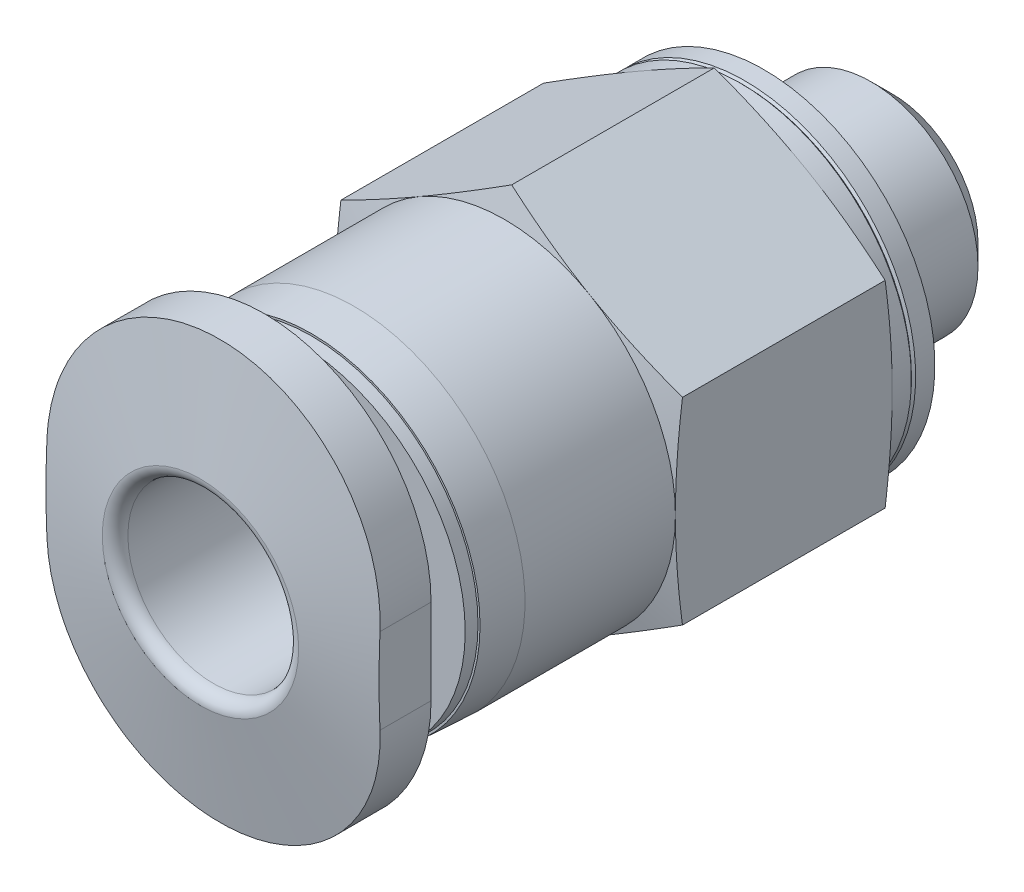
SolidWorks part; units mm, degrees
ref_plane "Front Plane" through (0, 0, 0) normal (0, 0, 1) x (1, 0, 0)
ref_plane "Top Plane" through (0, 0, 0) normal (0, 1, 0) x (1, 0, 0)
ref_plane "Right Plane" through (0, 0, 0) normal (1, 0, 0) x (0, 0, -1)
sketch "Sketch1" plane through (0, 0, 0) normal (1, 0, 0) x (0, 0, -1)
  line L0 (-13.2, 0) -> (-13.2, 2.3)
  line L1 (-13.2, 2.3) -> (-12.7354, 4.9347)
  line L2 (-12.5385, 5.1) -> (-11.7, 5.1)
  line L3 (-11.7, 5.1) -> (-11.7, 3.075)
  line L4 (-11.325, 2.7) -> (-10.9, 2.7)
  line L5 (-10.9, 2.7) -> (-10.9, 3.9)
  line L6 (-10.9, 3.9) -> (-10.6, 3.9)
  line L7 (-10.6, 3.9) -> (-10.6, 3.9476)
  line L8 (-10.6, 3.9476) -> (-9.6, 4)
  line L9 (-9.6, 4) -> (-6.0769, 4)
  line L10 (-6.0769, 4) -> (-5.9054, 4.64)
  line L11 (-5.9054, 4.64) -> (-1.1715, 4.64)
  line L12 (-1.1715, 4.64) -> (-1, 4)
  line L13 (-1, 4) -> (-0.55, 4)
  line L14 (-0.55, 4) -> (-0.5, 3.95)
  line L15 (-0.5, 3.95) -> (-0.45, 4)
  line L16 (-0.45, 4) -> (0, 4)
  line L17 (0, 4) -> (0, 0)
  line L18 (0, 0) -> (-13.2, 0)
  line L19 (0, 0) -> (-13.2, 0) construction
  arc A0 (-12.7354, 4.9347) -> (-12.5385, 5.1) centre (-12.5385, 4.9) cw
  arc A1 (-11.7, 3.075) -> (-11.325, 2.7) centre (-11.325, 3.075) ccw
revolve "Revolve1" add sketch "Sketch1" angle 360 about L19
ref_plane "Plane1" through (-13.2, 0, 0) normal (1, 0, 0) x (0, 0, -1)
ref_plane "Plane2" through (0, 0, 13.2) normal (0, 0, 1) x (1, 0, 0)
ref_plane "Plane3" through (0, 0, 9.7) normal (0, 0, 1) x (1, 0, 0)
sketch "Sketch2" plane through (0, 0, 13.2) normal (0, 0, 1) x (1, 0, 0)
  line L0 (-5.88, -3.3948) -> (0, -6.7896)
  line L1 (0, -6.7896) -> (5.88, -3.3948)
  line L2 (5.88, -3.3948) -> (5.88, 3.3948)
  line L3 (5.88, 3.3948) -> (0, 6.7896)
  line L4 (0, 6.7896) -> (-5.88, 3.3948)
  line L5 (-5.88, 3.3948) -> (-5.88, -3.3948)
  line L6 (-3.9, 1) -> (-3.9, -1)
  line L7 (3.9, -1) -> (3.9, 1)
  arc A0 (-3.9, -1) -> (0, -4.9) centre (0, -1) ccw
  arc A1 (0, -4.9) -> (3.9, -1) centre (0, -1) ccw
  arc A2 (3.9, 1) -> (0, 4.9) centre (0, 1) ccw
  arc A3 (0, 4.9) -> (-3.9, 1) centre (0, 1) ccw
extrude "Cut-Extrude1" cut sketch "Sketch2" against normal blind 1.5
sketch "Sketch3" plane through (0, 0, 0) normal (0, 0, 1) x (1, 0, 0)
  line L0 (-8, -8) -> (8, -8)
  line L1 (8, -8) -> (8, 8)
  line L2 (8, 8) -> (-8, 8)
  line L3 (-8, 8) -> (-8, -8)
  line L4 (-4, -2.3094) -> (0, -4.6188)
  line L5 (0, -4.6188) -> (4, -2.3094)
  line L6 (4, -2.3094) -> (4, 2.3094)
  line L7 (4, 2.3094) -> (0, 4.6188)
  line L8 (0, 4.6188) -> (-4, 2.3094)
  line L9 (-4, 2.3094) -> (-4, -2.3094)
extrude "Cut-Extrude2" cut sketch "Sketch3" along normal blind 7.7
ref_plane "Plane4" through (0, 0, 0) normal (1, 0, 0) x (0, 0, -1)
sketch "Sketch4" plane through (0, 0, 0) normal (1, 0, 0) x (0, 0, -1)
  line L0 (0, 0) -> (0, 2.5)
  line L1 (0, 2.5) -> (2.5095, 2.5)
  line L2 (2.5095, 2.5) -> (3, 2.0095)
  line L3 (3, 2.0095) -> (3, 0)
  line L4 (3, 0) -> (0, 0)
  line L5 (3, 0) -> (0, 0) construction
revolve "Revolve2" add sketch "Sketch4" angle 360 about L5 reverse direction yes
cosmetic thread "Cosmetic Thread1" parameters "D1"=3, "D2"=4.019
sketch "Sketch5" plane through (0, 0, 0) normal (1, 0, 0) x (0, 0, -1)
  line L0 (-13.2, 0) -> (-13.2, 2.3)
  line L1 (-12.9, 2) -> (-1.7, 2)
  line L2 (-1.7, 2) -> (-1.7, 1.1)
  line L3 (-1.7, 1.1) -> (3, 1.1)
  line L4 (3, 1.1) -> (3, 0)
  line L5 (3, 0) -> (-13.2, 0)
  line L6 (3, 0) -> (-13.2, 0) construction
  arc A0 (-13.2, 2.3) -> (-12.9, 2) centre (-12.9, 2.3) ccw
revolve "Cut-Revolve1" cut sketch "Sketch5" angle 360 about L6
ref_plane "Plane5" through (0, 0, 1.7) normal (0, 0, 1) x (1, 0, 0)
ref_plane "ANBAU XY" through (0, 0, 0) normal (0, 0, -1) x (-1, 0, 0)
ref_plane "ANBAU XZ" through (0, 0, 0) normal (0, 1, 0) x (1, 0, 0)
ref_plane "ANBAU YZ" through (0, 0, 0) normal (1, 0, 0) x (0, 0, -1)
ref_axis "ANBAU X" through (-80.9, 0, 0) along (1, 0, 0)
ref_axis "ANBAU Y" through (0, 50, 0) along (0, -1, 0)
ref_axis "ANBAU Z" through (0, 0, -80.9) along (0, 0, 1)
sketch3d "ANBAU"
  point P0 (0, 0, 0)
ref_plane "ANBAU_STD XY" through (0, 0, 0) normal (0, 0, 1) x (1, 0, 0)
ref_plane "ANBAU_STD XZ" through (0, 0, 0) normal (0, -1, 0) x (-1, 0, 0)
ref_plane "ANBAU_STD YZ" through (0, 0, 0) normal (1, 0, 0) x (0, 0, -1)
ref_axis "ANBAU_STD X" through (-80.9, 0, 0) along (1, 0, 0)
ref_axis "ANBAU_STD Y" through (0, -50, 0) along (0, 1, 0)
ref_axis "ANBAU_STD Z" through (0, 0, 80.9) along (0, 0, -1)
sketch3d "ANBAU_STD"
  point P0 (0, 0, 0)
ref_plane "FDT_SCHLAUCH XY" through (0, 0, 1.7) normal (0, 0, 1) x (1, 0, 0)
ref_plane "FDT_SCHLAUCH XZ" through (0, 0, 0) normal (0, -1, 0) x (-1, 0, 0)
ref_plane "FDT_SCHLAUCH YZ" through (0, 0, 0) normal (1, 0, 0) x (0, 0, -1)
ref_axis "FDT_SCHLAUCH X" through (-80.9, 0, 1.7) along (1, 0, 0)
ref_axis "FDT_SCHLAUCH Y" through (0, -50, 1.7) along (0, 1, 0)
ref_axis "FDT_SCHLAUCH Z" through (0, 0, 80.9) along (0, 0, -1)
sketch3d "FDT_SCHLAUCH"
  point P0 (0, 0, 1.7)
